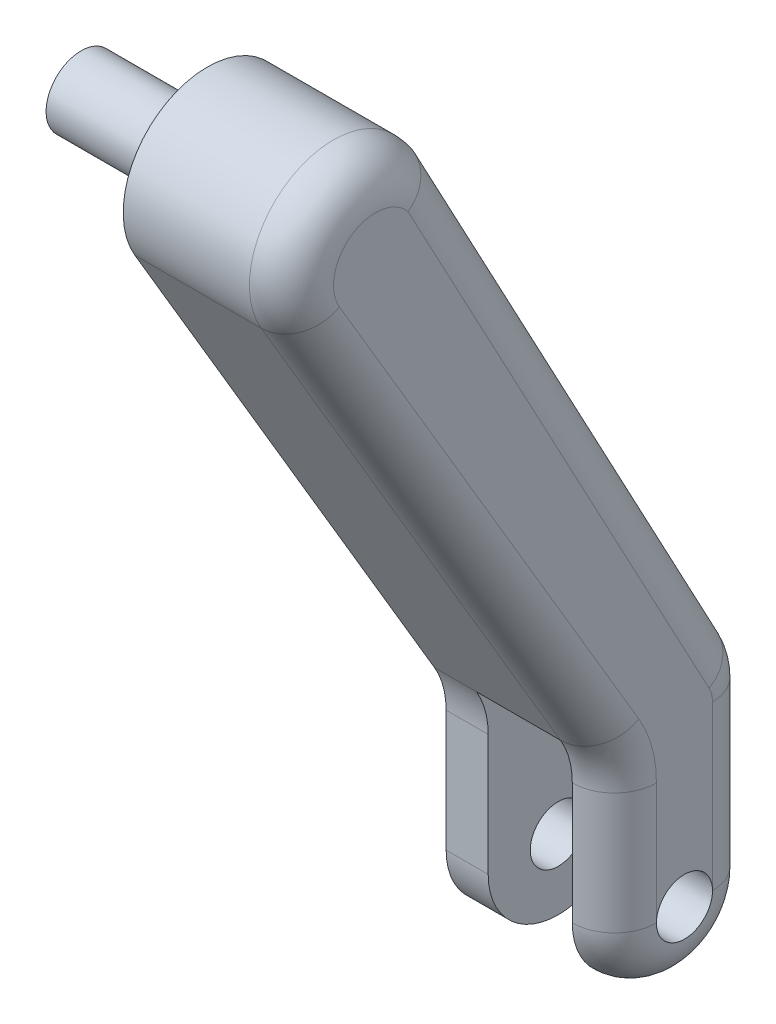
SolidWorks part; units mm, degrees
ref_plane "Front Plane" through (0, 0, 0) normal (0, 0, 1) x (1, 0, 0)
ref_plane "Top Plane" through (0, 0, 0) normal (0, 1, 0) x (1, 0, 0)
ref_plane "Right Plane" through (0, 0, 0) normal (1, 0, 0) x (0, 0, -1)
sketch "Sketch1" plane through (0, 0, 0) normal (1, 0, 0) x (0, 0, -1)
  circle A0 centre (0, 0) radius 30
  dimension "D1" = 60
extrude "Boss-Extrude1" add sketch "Sketch1" along normal blind 20
sketch "Sketch2" plane through (0, 0, 0) normal (-1, 0, 0) x (0, 0, 1)
  circle A0 centre (0, 0) radius 12.5
  dimension "D1" = 25
extrude "Boss-Extrude2" add sketch "Sketch2" along normal blind 45
sketch "Sketch3" plane through (20, 0, 0) normal (1, 0, 0) x (0, 0, -1)
  line L0 (-25.8251, -15.2665) -> (80.9913, -195.959)
  line L1 (0, 0) -> (110.1662, -196.1846) construction
  line L2 (85.1662, -211.2255) -> (85.1662, -254.4573)
  line L4 (135.1662, -254.4573) -> (135.1662, -196.1846)
  line L5 (11.3761, 41.7249) -> (132.0992, -184.1869)
  line L6 (11.3761, 41.7249) -> (-15.3737, 25.7614)
  arc A0 (135.1662, -196.1846) -> (132.0992, -184.1869) centre (110.1662, -196.1846) ccw
  circle A1 centre (0, 0) radius 30 construction
  arc A2 (85.1662, -254.4573) -> (135.1662, -254.4573) centre (110.1662, -254.4573) ccw
  arc A3 (85.1662, -211.2255) -> (80.9913, -195.959) centre (55.1662, -211.2255) ccw
  circle A4 centre (110.1662, -254.4573) radius 10
  circle A7 centre (0, 0) radius 30
  arc A8 (26.3195, 14.3973) -> (14.6888, -26.158) centre (0, 0) ccw
  circle A10 centre (0, 0) radius 30
  circle A11 centre (0, 0) radius 30
  point P22 (0, 0)
  circle M6 centre (0, 0) radius 30
  dimension "D1" = 50
  dimension "D3" = 30
  dimension "D4" = 20
  dimension "D2" = 225
  dimension "D5" = 0
  dimension "D6" = 0
extrude "Boss-Extrude4" add sketch "Sketch3" along normal blind 40 and the other way blind 20 contours M6 | A3 L2 A2 L4 A0 L5 L6 L0 A4 M6 region at (20, -137.5026, -72.3461) region at (20, -0.0085, 0.0159)
ref_plane "Plane1" through (30, 0, 0) normal (1, 0, 0) x (0, 0, -1)
sketch "Sketch4" plane through (30, 0, 0) normal (1, 0, 0) x (0, 0, -1)
  line L12 (24.1943, 17.738) -> (132.0992, -184.1869) construction
  line L16 (80.9913, -195.959) -> (127.0269, -174.6952)
  line L19 (85.1662, -254.4573) -> (85.1662, -211.2255)
  line L20 (85.1662, -254.4573) -> (85.1662, -211.2255)
  line L24 (24.1943, 17.738) -> (132.0992, -184.1869) construction
  line L26 (132.0992, -184.1869) -> (24.1943, 17.738)
  line L27 (135.1662, -254.4573) -> (135.1662, -196.1846)
  line L28 (132.0992, -184.1869) -> (127.0269, -174.6952)
  line L29 (135.1662, -254.4573) -> (135.1662, -196.1846)
  arc A15 (85.1662, -211.2255) -> (80.9913, -195.959) centre (55.1662, -211.2255) ccw
  arc A16 (85.1662, -211.2255) -> (80.9913, -195.959) centre (55.1662, -211.2255) ccw
  arc A24 (135.1662, -196.1846) -> (132.0992, -184.1869) centre (110.1662, -196.1846) ccw
  arc A25 (85.1662, -254.4573) -> (135.1662, -254.4573) centre (110.1662, -254.4573) ccw
  arc A26 (135.1662, -196.1846) -> (132.0992, -184.1869) centre (110.1662, -196.1846) ccw
  arc A27 (85.1662, -254.4573) -> (135.1662, -254.4573) centre (110.1662, -254.4573) ccw
  point P0 (127.0269, -174.6952)
  dimension "D1" = 0
  dimension "D2" = 0
extrude "Cut-Extrude1" cut sketch "Sketch4" against normal mid plane 30
fillet "Fillet2" radius 15 8 edges at (60, -83.2244, -78.1467) (60, -189.9928, -134.3873) (60, -225.321, -135.1662) (60, -279.4573, -110.1662) (60, -232.8414, -85.1662) (60, -203.312, -84.1037) (60, -105.6127, -27.5831) (60, 25.0402, 16.5224)
